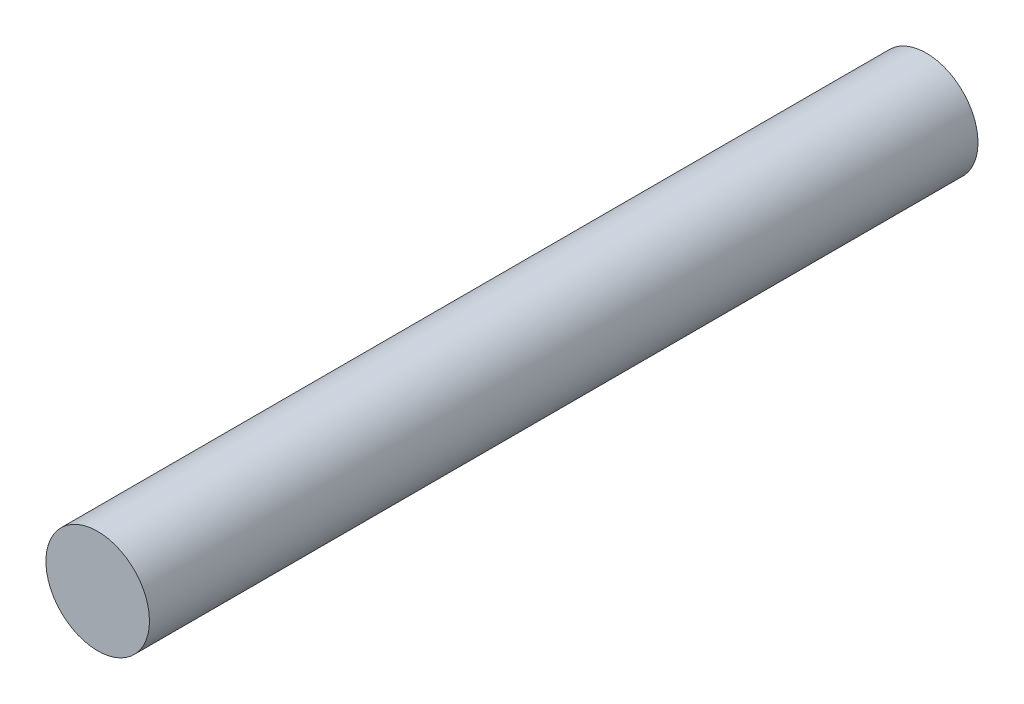
SolidWorks part; units mm, degrees
ref_plane "Front Plane" through (0, 0, 0) normal (0, 0, 1) x (1, 0, 0)
ref_plane "Top Plane" through (0, 0, 0) normal (0, 1, 0) x (1, 0, 0)
ref_plane "Right Plane" through (0, 0, 0) normal (1, 0, 0) x (0, 0, -1)
sketch "Sketch1" plane through (0, 0, 0) normal (0, 0, 1) x (1, 0, 0)
  circle A0 centre (0, 0) radius 6.35
  dimension "D1" = 12.7
extrude "Boss-Extrude1" add sketch "Sketch1" along normal blind 50.8 and the other way blind 50.8
